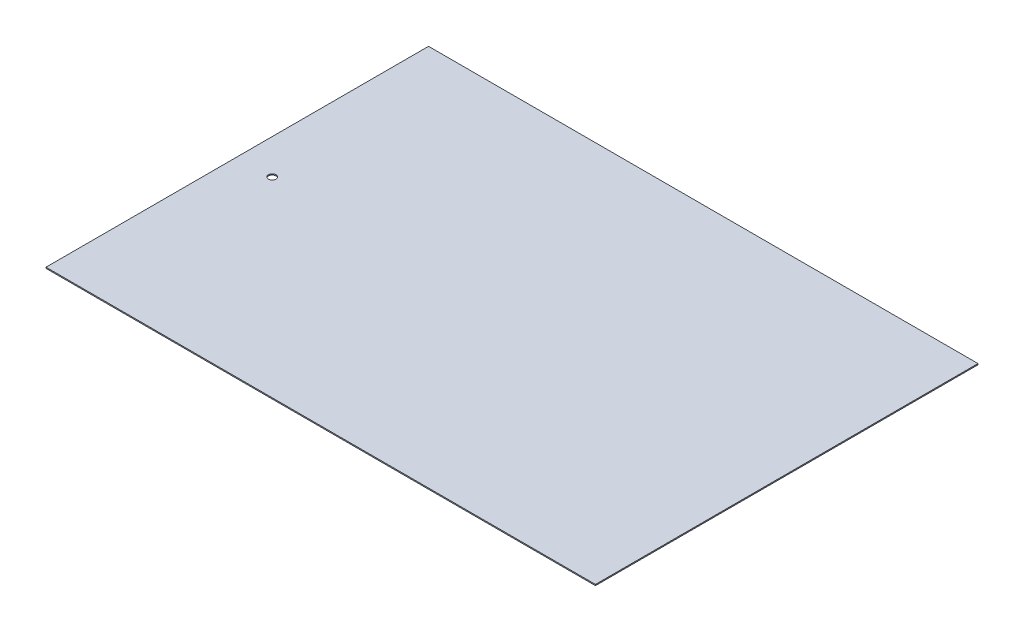
SolidWorks part; units mm, degrees
material "Acrylic (Medium-high impact)"
ref_plane "Front Plane" through (0, 0, 0) normal (0, 0, 1) x (1, 0, 0)
ref_plane "Top Plane" through (0, 0, 0) normal (0, 1, 0) x (1, 0, 0)
ref_plane "Right Plane" through (0, 0, 0) normal (1, 0, 0) x (0, 0, -1)
sketch "Sketch1" plane through (0, 0, 0) normal (0, 1, 0) x (1, 0, 0)
  line L1 (-790, -550) -> (790, -550) construction
  line L2 (-790, -550) -> (-790, 550) construction
  line L3 (-790, 550) -> (790, 550) construction
  line L4 (790, -550) -> (790, 550) construction
  line L5 (-790, -550) -> (790, 550) construction
  line L6 (-790, 550) -> (790, -550) construction
  point P0 (0, 0)
  dimension "Length" = 1580
  dimension "Width" = 1100
sketch "Sketch2" plane through (0, 0, 0) normal (1, 0, 0) x (0, 0, -1)
  line L1 (-550, -1.5875) -> (550, -1.5875) construction
  line L2 (-550, -1.5875) -> (-550, 1.5875) construction
  line L3 (-550, 1.5875) -> (550, 1.5875) construction
  line L4 (550, -1.5875) -> (550, 1.5875) construction
  line L5 (-550, -1.5875) -> (550, 1.5875) construction
  line L6 (-550, 1.5875) -> (550, -1.5875) construction
  dimension "Thickness" = 3.175
sketch "Sketch3" plane through (0, 0, 0) normal (1, 0, 0) x (0, 0, -1)
  line L1 (550, 1.5875) -> (-550, 1.5875)
  line L2 (550, 1.5875) -> (550, -1.5875)
  line L3 (550, -1.5875) -> (-550, -1.5875)
  line L4 (-550, 1.5875) -> (-550, -1.5875)
extrude "Boss-Extrude1" add sketch "Sketch3" against normal up to vertex (790 mm away) and the other way up to vertex (790 mm away) up to point (-790, 0, -550) other way up to point (790, 0, -550)
sketch "Sketch4" plane through (0, 1.5875, 0) normal (0, 1, 0) x (1, 0, 0)
  circle A0 centre (-689.5325, 0) radius 11
  dimension "D1" = 22
extrude "Cut-Extrude1" cut sketch "Sketch4" against normal blind 10
